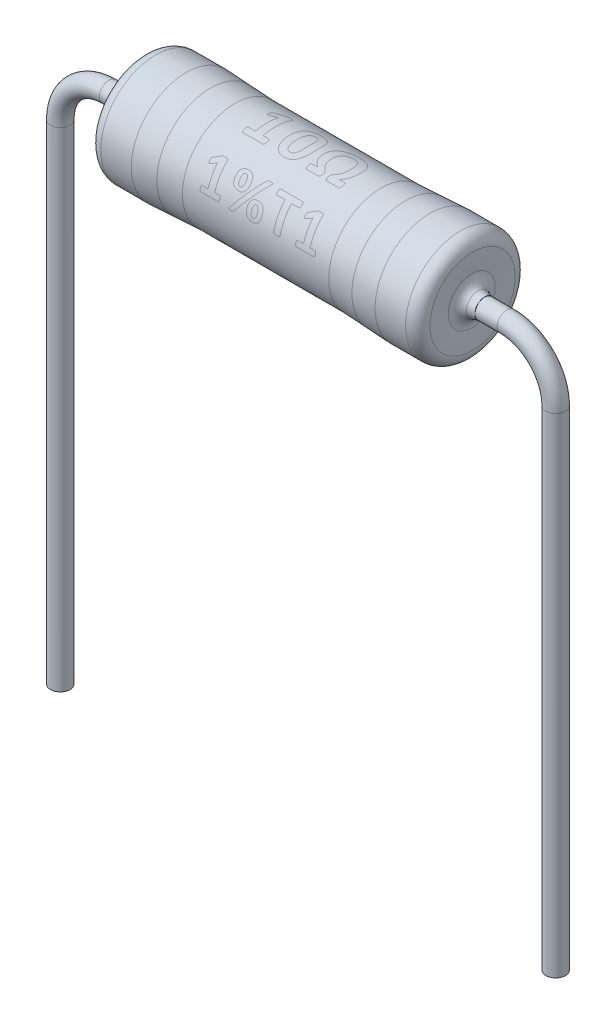
SolidWorks part; units mm, degrees
other "WIRE"
other "RESISTOR"
ref_plane "Front Plane" through (0, 0, 0) normal (0, 0, 1) x (1, 0, 0)
ref_plane "Top Plane" through (0, 0, 0) normal (0, 1, 0) x (1, 0, 0)
ref_plane "Right Plane" through (0, 0, 0) normal (1, 0, 0) x (0, 0, -1)
sketch "Sketch Wire Length" plane through (0, 0, 0) normal (0, 0, 1) x (1, 0, 0)
  line L0 (-8.16, 0) -> (8.16, 0)
  line L1 (10.16, -2) -> (10.16, -22.0484)
  line L2 (-10.16, -2) -> (-10.16, -22.0484)
  arc A0 (-8.16, 0) -> (-10.16, -2) centre (-8.16, -2) ccw
  arc A1 (8.16, 0) -> (10.16, -2) centre (8.16, -2) cw
  dimension "D2" = 2
  dimension "D3" = 62.7
  dimension "D1" = 20.32
sketch "Sketch Wire Diameter" plane through (0, 0, 0) normal (1, 0, 0) x (0, 0, -1)
  circle A0 centre (0, 0) radius 0.4
  dimension "D1" = 0.8
sweep "SET WIRE LENGTH" add profiles "Sketch Wire Diameter" path "Sketch Wire Length"
sketch "Sketch4" plane through (0, 0, 0) normal (0, 0, 1) x (1, 0, 0)
  line L0 (-7.25, 0) -> (7.25, 0)
  line L1 (7.25, 0) -> (7.25, 0.41)
  line L2 (-7.25, 0) -> (-7.25, 0.41)
  line L3 (0, 0) -> (0, 2.15) construction
  line L4 (0, 2.15) -> (0, 2.2) construction
  line L5 (-3, 2.15) -> (3, 2.15)
  line L6 (-4, 2.2) -> (4, 2.2) construction
  line L7 (0, 2.2) -> (0, 2.25) construction
  line L8 (-5, 2.25) -> (5, 2.25) construction
  line L9 (-5, 2.25) -> (-6.75, 2.25)
  line L10 (5, 2.25) -> (6.75, 2.25)
  line L11 (-6.75, 2.25) -> (-6.75, 1.81)
  line L12 (6.75, 2.25) -> (6.75, 1.81)
  line L13 (-6.75, 1.81) -> (-6.75, 0.81) construction
  line L14 (-6.75, 0.81) -> (-6.7, 0.81) construction
  line L15 (6.75, 1.81) -> (6.75, 0.81) construction
  line L16 (6.75, 0.81) -> (6.7, 0.81) construction
  line L17 (-7.25, 0.41) -> (7.25, 0.41) construction
  arc A0 (-3, 2.15) -> (-4, 2.2) centre (-3, 12.175) cw
  arc A1 (3, 2.15) -> (4, 2.2) centre (3, 12.175) ccw
  arc A2 (-5, 2.25) -> (-4, 2.2) centre (-5, -7.775) cw
  arc A3 (4, 2.2) -> (5, 2.25) centre (5, -7.775) cw
  arc A4 (-6.75, 1.81) -> (-6.7, 0.81) centre (3.275, 1.81) ccw
  arc A5 (-7.25, 0.41) -> (-6.7, 0.81) centre (-7.25, 0.9881) ccw
  arc A6 (6.75, 1.81) -> (6.7, 0.81) centre (-3.275, 1.81) cw
  arc A7 (6.7, 0.81) -> (7.25, 0.41) centre (7.25, 0.9881) ccw
  dimension "D7" = 13.5
  dimension "D8" = 1
  dimension "D10" = 0.4
  dimension "D1" = 14.5
  dimension "D2" = 0.41
  dimension "D3" = 2.15
  dimension "D4" = 2.25
  dimension "D5" = 6
  dimension "D6" = 8
  dimension "D9" = 0.05
revolve "Revolve1" add sketch "Sketch4" angle 360 about L0
fillet "Fillet1" radius 0.5 2 edges at (6.7, -0.81, 0) (-6.7, -0.81, 0)
fillet "Fillet2" radius 0.5 2 edges at (6.75, -2.25, 0) (-6.75, -2.25, 0)
ref_plane "Plane1" through (0, 10, 0) normal (0, 1, 0) x (1, 0, 0)
sketch "SketchSpecs" plane through (0, 10, 0) normal (0, 1, 0) x (1, 0, 0)
  line L0 (0, 0.75) -> (0, -0.75) construction
  line L1 (-3, -0.75) -> (3, -0.75) construction
  line L2 (-3, -2.15) -> (-3, 2.15) construction
  line L3 (0, 0.75) -> (0, 1.55) construction
  line L4 (-3, 1.55) -> (3, 1.55) construction
  line L5 (0, -0.75) -> (0, -2.95) construction
  line L6 (-3, -2.95) -> (3, -2.95) construction
  text T0 "10Ω" font "Calibri" height 1.5
  text T1 "CPF 3" font "Calibri" height 1.3
  text T2 "1%T1" font "Calibri" height 1.3
  dimension "D1" = 1.5
  dimension "D2" = 0.8
  dimension "D3" = 2.2
wrap "Wrap SPECS" sketch "SketchSpecs" wrap type scribe source sketch "SketchSpecs" face at (-3, -2.15, 0)
ref_plane "Plane2" through (0, -4, 0) normal (0, 1, 0) x (1, 0, 0)
sketch "Sketch5" plane through (0, -4, 0) normal (0, 1, 0) x (1, 0, 0)
  line L0 (0, -0.6) -> (0, 0) construction
  line L1 (0, 0) -> (0, 2) construction
  line L2 (-3, -0.6) -> (3, -0.6) construction
  line L3 (-3, 2) -> (3, 2) construction
  line L4 (-3, -2.15) -> (-3, 2.15) construction
  text T0 "DALE" font "Calibri" height 1.4
  text T1 "1841" font "Calibri" height 1.4
  dimension "D1" = 0.6
  dimension "D2" = 2
wrap "Wrap1" sketch "Sketch5" wrap type scribe source sketch "Sketch5" face at (-3, -2.15, 0)
